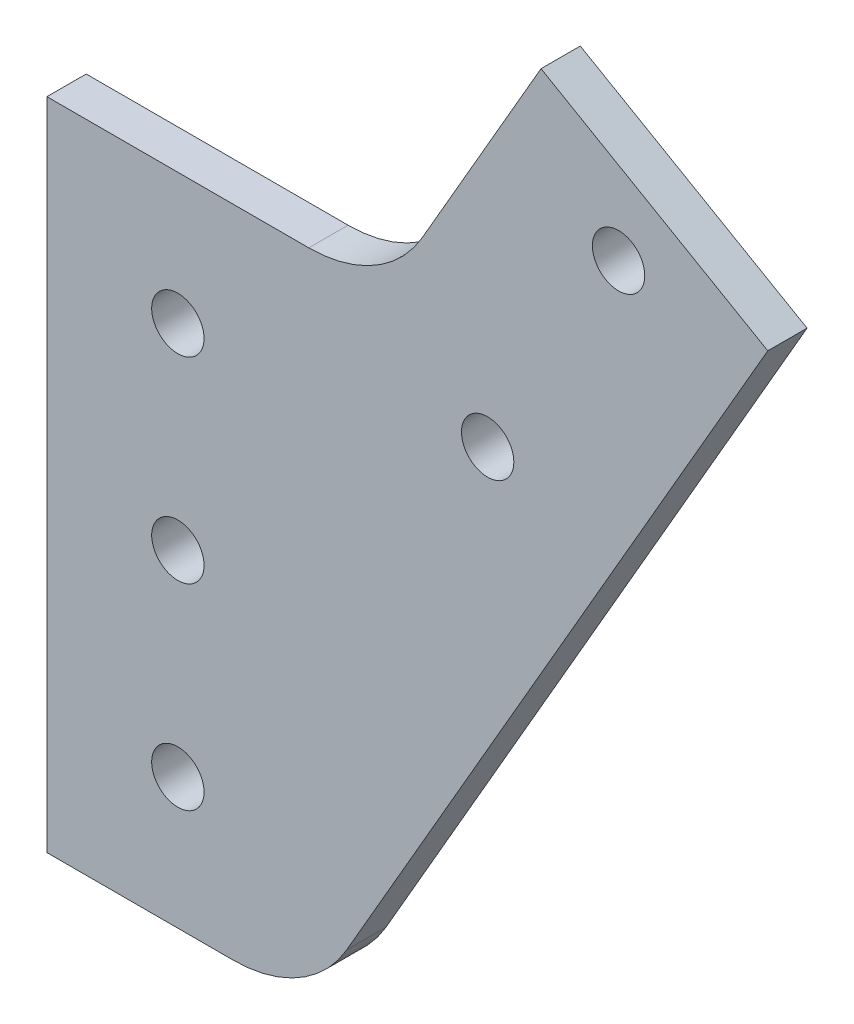
SolidWorks part; units mm, degrees
ref_plane "前视基准面" through (0, 0, 0) normal (0, 0, 1) x (1, 0, 0)
ref_plane "上视基准面" through (0, 0, 0) normal (0, 1, 0) x (1, 0, 0)
ref_plane "右视基准面" through (0, 0, 0) normal (1, 0, 0) x (0, 0, -1)
sketch "草图1" plane through (0, 0, 0) normal (0, 0, 1) x (1, 0, 0)
  line L0 (10, 15) -> (27.3205, 5)
  line L1 (-10, 25) -> (10, 25)
  line L2 (-10, 25) -> (-10, -25)
  line L3 (-10, -25) -> (10, -25)
  line L4 (10, 25) -> (10, -25)
  line L5 (-10, 25) -> (10, -25) construction
  line L6 (-10, -25) -> (10, 25) construction
  line L7 (10, 15) -> (27.7357, 45.7191)
  line L8 (27.3205, 5) -> (45.0562, 35.7191)
  line L9 (27.7357, 45.7191) -> (45.0562, 35.7191)
  line L10 (10, 15) -> (45.0562, 35.7191) construction
  line L11 (27.3205, 5) -> (27.7357, 45.7191) construction
  line L12 (27.3205, 5) -> (10, -25)
  line L13 (0, -999.5031) -> (0, 49000.4969) construction
  line L14 (36.3959, 40.7191) -> (18.6603, 10) construction
  circle A0 centre (0, 15) radius 2
  circle A1 centre (0, -15) radius 2
  circle A2 centre (0, 0) radius 2
  circle A3 centre (23.6603, 18.6603) radius 2
  circle A4 centre (33.6603, 35.9808) radius 2
  point P0 (0, 0)
  point P6 (27.5281, 25.3596)
  dimension "D6" = 4
  dimension "D7" = 4
  dimension "D8" = 4
  dimension "D9" = 15
  dimension "D10" = 15
  dimension "D11" = 4
  dimension "D12" = 4
  dimension "D13" = 10
  dimension "D14" = 20
  dimension "D1" = 50
  dimension "D2" = 20
  dimension "D3" = 20
  dimension "D4" = 35.4714
  dimension "D5" = 120
extrude "凸台-拉伸1" add sketch "草图1" along normal blind 3 contours L12 L0 L4 | L9 L7 L0 L8 A4 A3 | L4 L1 L2 L3 A2 A1 A0
fillet "圆角1" radius 10 2 edges at (10, -25, 1.5) (10, 15, 1.5)
